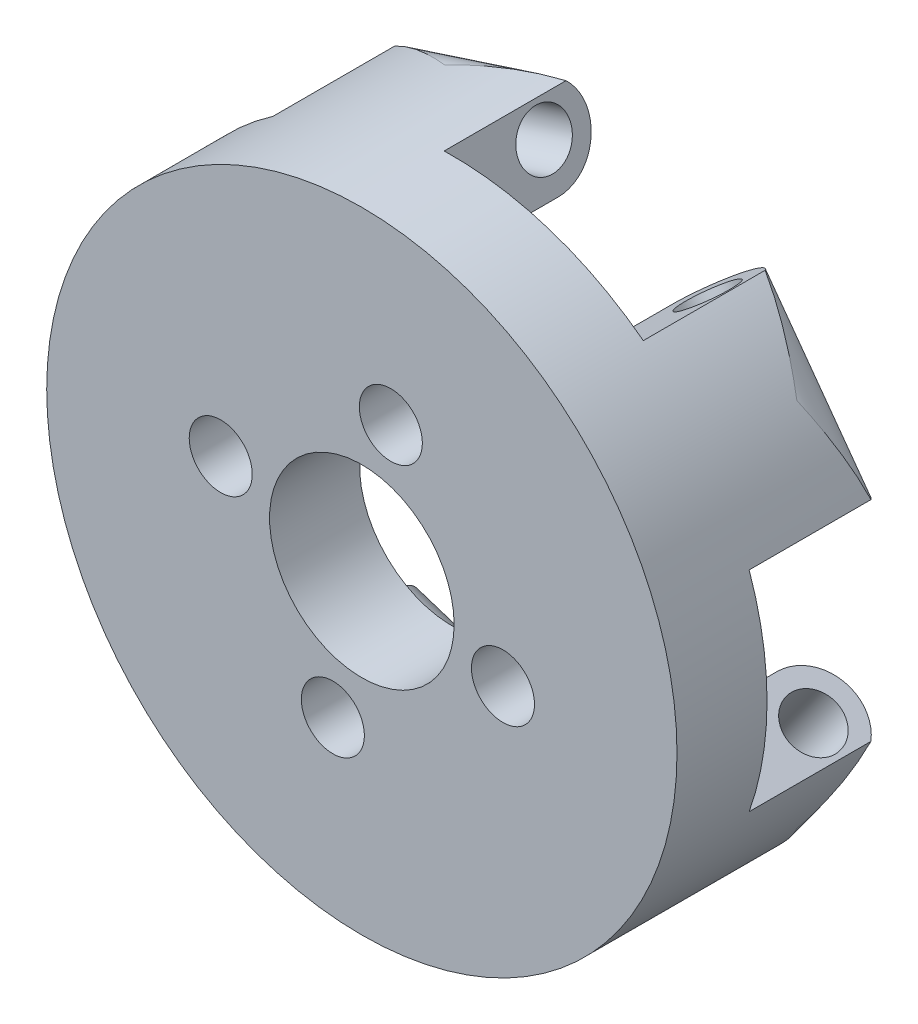
SolidWorks part; units mm, degrees
ref_plane "Plan de face" through (0, 0, 0) normal (0, 0, 1) x (1, 0, 0)
ref_plane "Plan de dessus" through (0, 0, 0) normal (0, 1, 0) x (1, 0, 0)
ref_plane "Plan de droite" through (0, 0, 0) normal (1, 0, 0) x (0, 0, -1)
sketch "Esquisse1" plane through (0, 0, 0) normal (0, 0, 1) x (1, 0, 0)
  circle A0 centre (0, 0) radius 17.5
  circle A1 centre (0, 0) radius 5.125
  dimension "D1" = 35
  dimension "D2" = 10.25
extrude "Boss.-Extru.1" add sketch "Esquisse1" along normal blind 5
sketch "Esquisse2" plane through (0, 0, 0) normal (0, 1, 0) x (1, 0, 0)
  line L1 (17.5, 0) -> (-17.5, 0) construction
  line L2 (-17.5, 0) -> (-17.5, 5)
  line L3 (-12.5, 0) -> (-12.5, 5)
  line L4 (-17.5, 0) -> (-12.5, 0)
  arc A0 (-17.5, 5) -> (-12.5, 5) centre (-15, 5) cw
  circle A1 centre (-15, 5) radius 1.5
  dimension "D2" = 3
  dimension "D1" = 5
  dimension "D3" = 5
extrude "Boss.-Extru.2" add sketch "Esquisse2" along normal blind 5 and the other way blind 5
sketch "Esquisse3" plane through (0, 0, 0) normal (0, 0, 1) x (1, 0, 0)
  line L0 (-17.5, 0) -> (-17.5, -5) construction
  line L1 (-17.5, -5) -> (-16.7705, -5) construction
  line L2 (-16.7705, 5) -> (-17.5, 5) construction
  line L3 (-17.5, 5) -> (-17.5, 0) construction
  line L4 (-17.5, 0) -> (-17.5, -5)
  line L5 (-17.5, -5) -> (-16.7705, -5)
  line L6 (-16.7705, 5) -> (-17.5, 5)
  line L7 (-17.5, 5) -> (-17.5, 0)
  arc A0 (-17.5, 0) -> (-16.7705, -5) centre (0, 0) ccw construction
  arc A1 (-16.7705, 5) -> (-17.5, 0) centre (0, 0) ccw construction
  arc A2 (-17.5, 0) -> (-16.7705, -5) centre (0, 0) ccw
  arc A3 (-16.7705, 5) -> (-17.5, 0) centre (0, 0) ccw
  arc M1 (-17.5, 0) -> (-16.7705, 5) centre (0, 0) cw
  line M2 (-16.7705, 5) -> (-17.5, 5)
  line M3 (-17.5, 5) -> (-17.5, 0)
extrude "Enlèv. mat.-Extru.1" cut sketch "Esquisse3" against normal through all contours M3 M1 M2 | A2 L4 L5 region at (-17.282, -3.7553, 0) region at (-17.282, 3.7553, 0)
pattern_circular "Répétition circulaire1" count 5 over 360 about axis through (0, 0, 0) along (0, 0, 1) of "Enlèv. mat.-Extru.1", "Boss.-Extru.2"
sketch "Esquisse4" plane through (0, 0, 0) normal (0, 0, -1) x (-1, 0, 0)
  circle A0 centre (-7.8364, -1.6098) radius 1.75
  circle A1 centre (1.6098, -7.8364) radius 1.75
  circle A2 centre (7.8364, 1.6098) radius 1.75
  circle A3 centre (-1.6098, 7.8364) radius 1.75
extrude "Enlèv. mat.-Extru.2" cut sketch "Esquisse4" against normal blind 10
